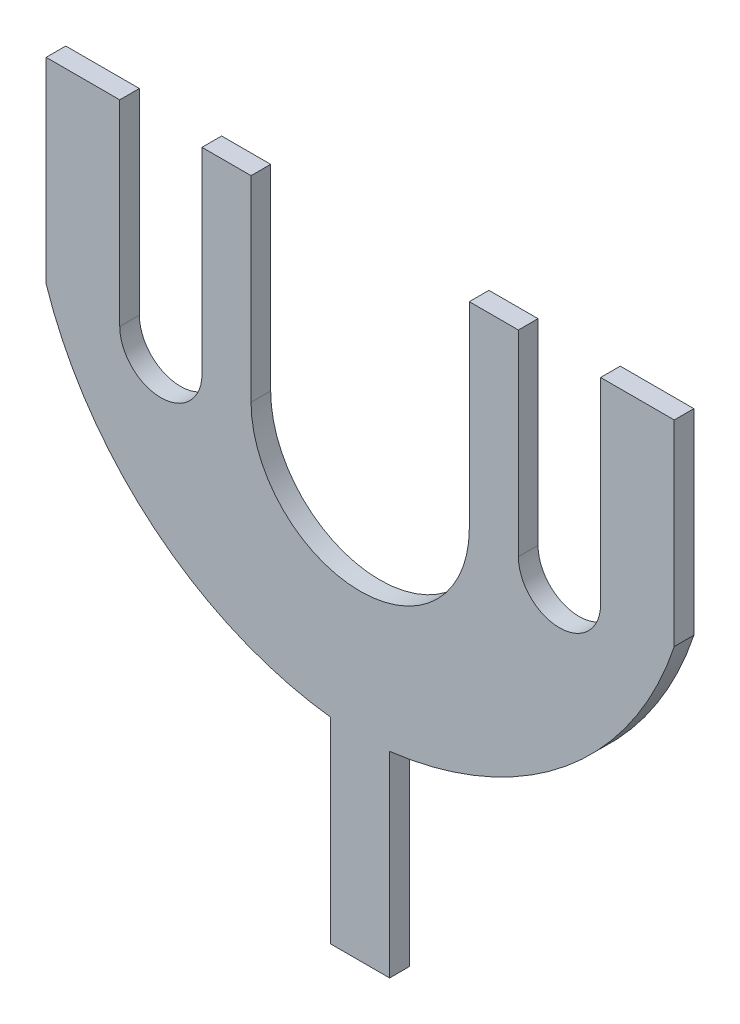
SolidWorks part; units mm, degrees
material "6061-T4 (SS)"
ref_plane "Front Plane" through (0, 0, 0) normal (0, 0, 1) x (1, 0, 0)
ref_plane "Top Plane" through (0, 0, 0) normal (0, 1, 0) x (1, 0, 0)
ref_plane "Right Plane" through (0, 0, 0) normal (1, 0, 0) x (0, 0, -1)
sketch "Sketch2" plane through (0, 0, 0) normal (0, 0, 1) x (1, 0, 0)
  line L0 (-21, 21.4878) -> (-17.25, 21.4878)
  line L1 (-21, 21.4878) -> (-21, 11.4878)
  line L2 (-10.56, 21.4878) -> (-10.56, 11.4878)
  line L3 (3.06, 21.4878) -> (3.06, 11.4878)
  line L4 (-21, 11.4878) -> (11, 11.4878) construction
  line L5 (11, 21.4878) -> (11, 8.9983) construction
  line L6 (-5, 11.4878) -> (-5, -10.3842) construction
  line L9 (-17.25, 11.4878) -> (-17.25, 21.4878)
  line L10 (11, 21.4878) -> (-25, 21.4878) construction
  line L13 (-13.06, 11.4878) -> (-13.06, 21.4878)
  line L14 (-13.06, 21.4878) -> (-10.56, 21.4878)
  line L16 (7.25, 11.4878) -> (7.25, 21.4878)
  line L17 (11, 11.4878) -> (11, 21.4878)
  line L23 (3.06, 21.4878) -> (0.56, 21.4878)
  line L24 (0.56, 21.4878) -> (0.56, 11.4878)
  line L25 (7.25, 21.4878) -> (11, 21.4878)
  line L28 (-6.5, -0.3842) -> (-6.5, -10.3842)
  line L29 (-6.5, -10.3842) -> (-3.5, -10.3842)
  line L30 (-3.5, -10.3842) -> (-3.5, -0.3842)
  arc A0 (-21, 11.4878) -> (-6.5, -0.3842) centre (-4.3868, 16.9878) ccw
  arc A2 (-17.25, 11.4878) -> (-13.06, 11.4878) centre (-15.155, 11.4878) ccw
  arc A3 (3.06, 11.4878) -> (7.25, 11.4878) centre (5.155, 11.4878) ccw
  arc A4 (-10.56, 11.4878) -> (0.56, 11.4878) centre (-5, 11.4878) ccw
  arc A5 (11, 11.4878) -> (-3.5, -0.3842) centre (-5.6132, 16.9878) cw
  point P4 (0, 0)
  point P5 (0, 0)
  point P6 (0, 0)
  point P9 (0, 0)
  point P10 (5.105, 11.9878)
  point P12 (0, 0)
  point P13 (0, 0)
  point P14 (5.105, 11.9878)
  dimension "D1" = 2.5
  dimension "D9" = 17.5
  dimension "D10" = 17.5
  dimension "D11" = 32
  dimension "D2" = 2.5
  dimension "D3" = 10
  dimension "D4" = 4.19
  dimension "D5" = 5.5
  dimension "D6" = 3
  dimension "D7" = 3.75
  dimension "D8" = 3.75
  dimension "D12" = 10
extrude "Boss-Extrude2" add sketch "Sketch2" along normal blind 1
